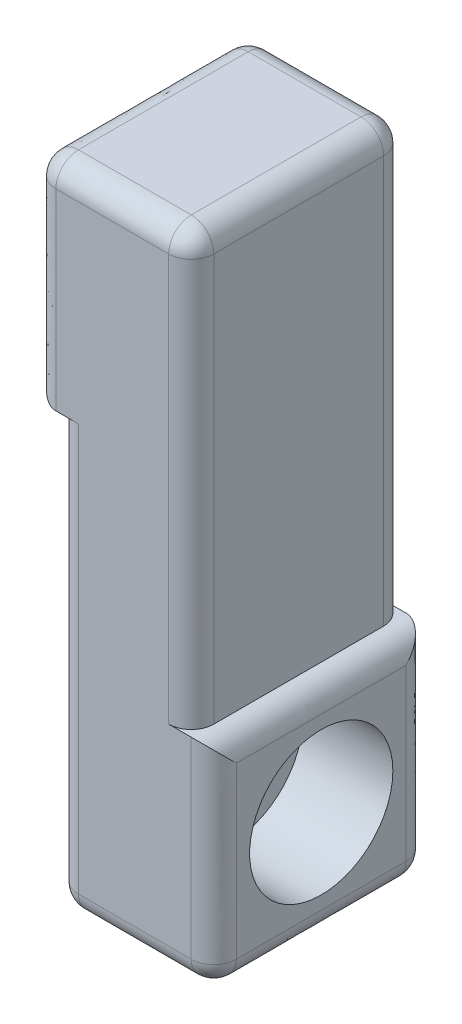
SolidWorks part; units mm, degrees
ref_plane "Front Plane" through (0, 0, 0) normal (0, 0, 1) x (1, 0, 0)
ref_plane "Top Plane" through (0, 0, 0) normal (0, 1, 0) x (1, 0, 0)
ref_plane "Right Plane" through (0, 0, 0) normal (1, 0, 0) x (0, 0, -1)
sketch "Sketch2" plane through (0, 0, 0) normal (1, 0, 0) x (0, 0, -1)
  line L1 (-4.7625, 14.2875) -> (4.7625, 14.2875)
  line L2 (-4.7625, 14.2875) -> (-4.7625, -14.2875)
  line L3 (-4.7625, -14.2875) -> (4.7625, -14.2875)
  line L4 (4.7625, 14.2875) -> (4.7625, -14.2875)
  line L5 (-4.7625, 14.2875) -> (4.7625, -14.2875) construction
  line L6 (-4.7625, -14.2875) -> (4.7625, 14.2875) construction
  point P0 (0, 0)
  dimension "D1" = 28.575
  dimension "D2" = 9.525
extrude "Boss-Extrude1" add sketch "Sketch2" along normal mid plane 6
ref_plane "Plane1" through (-3, 0, 0) normal (-1, 0, 0) x (0, 0, 1)
ref_plane "Plane2" through (3, 0, 0) normal (1, 0, 0) x (0, 0, -1)
sketch "Sketch5" plane through (-3, 0, 0) normal (-1, 0, 0) x (0, 0, 1)
  line L0 (4.7625, 14.2875) -> (4.7625, -14.2875) construction
  line L1 (-4.7625, 14.2875) -> (4.7625, 14.2875)
  line L2 (-4.7625, 14.2875) -> (-4.7625, 4.7625)
  line L3 (-4.7625, 4.7625) -> (4.7625, 4.7625)
  line L4 (4.7625, 14.2875) -> (4.7625, 4.7625)
  line L5 (-4.7625, 14.2875) -> (4.7625, 4.7625) construction
  line L6 (-4.7625, 4.7625) -> (4.7625, 14.2875) construction
  line L7 (-4.7625, 14.2875) -> (4.7625, 14.2875) construction
  point P0 (0, 9.525)
extrude "Boss-Extrude2" add sketch "Sketch5" along normal blind 1
sketch "Sketch7" plane through (3, 0, 0) normal (1, 0, 0) x (0, 0, -1)
  line L0 (4.7625, -14.2875) -> (4.7625, 14.2875) construction
  line L1 (-4.7625, -14.2875) -> (4.7625, -14.2875)
  line L2 (-4.7625, -14.2875) -> (-4.7625, -4.7625)
  line L3 (-4.7625, -4.7625) -> (4.7625, -4.7625)
  line L4 (4.7625, -14.2875) -> (4.7625, -4.7625)
  line L5 (-4.7625, -14.2875) -> (4.7625, -4.7625) construction
  line L6 (-4.7625, -4.7625) -> (4.7625, -14.2875) construction
  line L7 (-4.7625, -14.2875) -> (4.7625, -14.2875) construction
  point P0 (0, -9.525)
  dimension "D1" = 4.7625
extrude "Boss-Extrude3" add sketch "Sketch7" along normal blind 1
sketch "Sketch8" plane through (4, 0, 0) normal (1, 0, 0) x (0, 0, -1)
  line L0 (-4.7625, -14.2875) -> (4.7625, -14.2875) construction
  circle A0 centre (0, -9.525) radius 3.175
  dimension "D1" = 4.7625
extrude "Cut-Extrude2" cut sketch "Sketch8" against normal blind 4
sketch "Sketch9" plane through (-4, 0, 0) normal (-1, 0, 0) x (0, 0, 1)
  line L0 (4.7625, 14.2875) -> (-4.7625, 14.2875) construction
  circle A0 centre (0, 9.525) radius 3.175
  dimension "D1" = 4.7625
extrude "Cut-Extrude3" cut sketch "Sketch9" against normal blind 4
fillet "Fillet6" radius 1 14 edges at (4, -9.525, -4.7625) (4, -9.525, 4.7625) (-4, 9.525, 4.7625) (-4, 9.525, -4.7625) (0.5, -14.2875, -4.7625) (-3, -14.2875, 0) (0.5, -14.2875, 4.7625) (4, -14.2875, 0) (4, -4.7625, 0) (-4, 4.7625, 0) (-4, 14.2875, 0) (-0.5, 14.2875, 4.7625) (3, 14.2875, 0) (-0.5, 14.2875, -4.7625) first distance on face at (0, 0, -4.7625) first distance on face at (0, 0, 4.7625) first distance on face at (-3, -4.7625, 0) first distance on face at (0.5, -14.2875, 0) first distance on face at (3.5, -4.7625, 0) first distance on face at (-3.5, 4.7625, 0) first distance on face at (-4, 9.525, 3.175) first distance on face at (3, 4.7625, 0)
fillet "Fillet7" radius 1 8 edges at (-2.8712, -13.7785, -4.6337) (-3, -4.2625, -4.7625) (2.8712, 13.7785, -4.6337) (3, 4.2625, -4.7625) (2.8712, 13.7785, 4.6337) (3, 4.2625, 4.7625) (-2.8712, -13.7785, 4.6337) (-3, -4.2625, 4.7625) first distance on face at (-2.6856, -13.783, -0.25) first distance on face at (-3, -4.2625, -1.1906) first distance on face at (-0.2822, 13.9102, -4.2303) first distance on face at (3, 4.2625, -1.1906) first distance on face at (2.6856, 13.783, -0.25) first distance on face at (0.0322, -13.6602, 4.4803)
